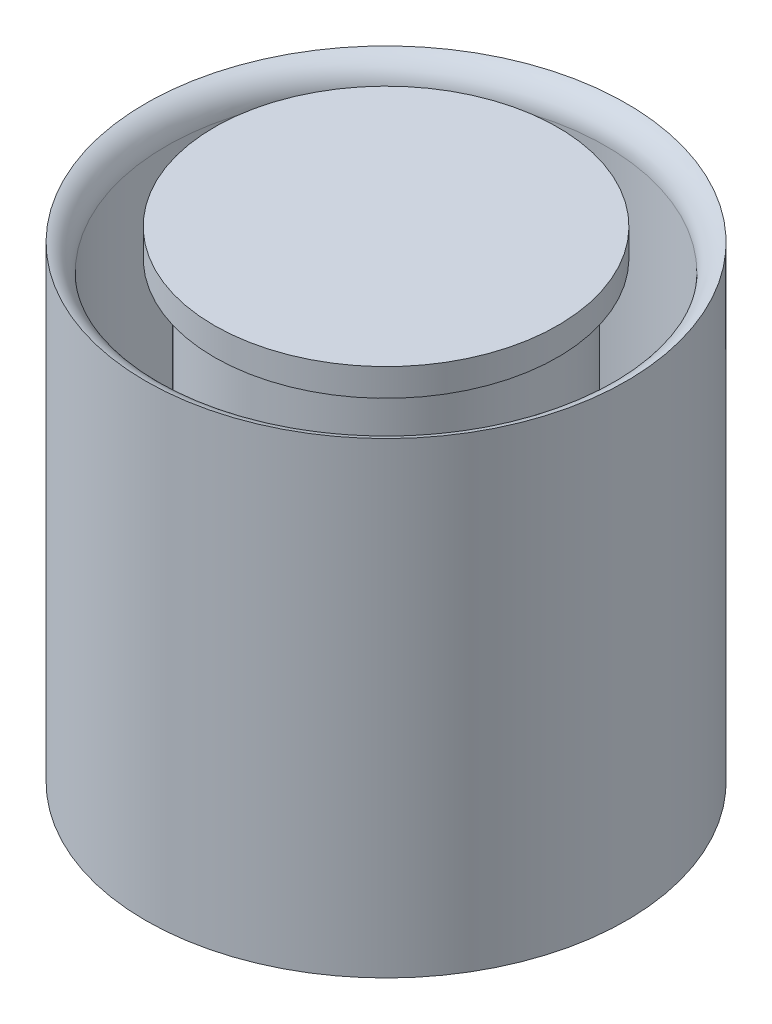
SolidWorks part; units mm, degrees
other "Markup1"
sketch "Sketch7" plane through (-27.825, 44.8441, 27.8252) normal (-0.0236, 0.9996, 0.0157) x (0.9993, 0.0241, -0.0277)
ref_plane "Alzado" through (0, 0, 0) normal (0, 0, 1) x (1, 0, 0)
ref_plane "Planta" through (0, 0, 0) normal (0, 1, 0) x (1, 0, 0)
ref_plane "Vista lateral" through (0, 0, 0) normal (1, 0, 0) x (0, 0, -1)
sketch "Sketch1" plane through (0, 0, 0) normal (0, 1, 0) x (1, 0, 0)
  circle A0 centre (0, 0) radius 17.5
  circle A1 centre (0, 0) radius 16
  dimension "D1" = 35
  dimension "D2" = 32
extrude "Boss-Extrude1" add sketch "Sketch1" along normal blind 34
sketch "Sketch2" plane through (0, 0, 0) normal (0, 1, 0) x (1, 0, 0)
  circle A0 centre (0, 0) radius 17.5
  dimension "D1" = 35
extrude "Boss-Extrude2" add sketch "Sketch2" along normal blind 3
fillet "Fillet1" radius 2 1 edges at (0, 34, 16)
ref_plane "Plane1" through (0, 3, 0) normal (0, 1, 0) x (1, 0, 0)
sketch "Sketch3" plane through (0, 3, 0) normal (0, 1, 0) x (1, 0, 0)
  circle A0 centre (0, 0) radius 11
  dimension "D1" = 22
extrude "Boss-Extrude3" add sketch "Sketch3" along normal blind 30
sketch "Sketch5" plane through (0, 33, 0) normal (0, 1, 0) x (1, 0, 0)
  line L0 (-1.0774, 1.3853) -> (1.0774, 1.3853)
  arc A0 (-1.0774, 1.3853) -> (1.0774, 1.3853) centre (0, 0) ccw
extrude "Cut-Extrude1" cut sketch "Sketch5" against normal blind 35
sketch "Sketch6" plane through (0, 33, 0) normal (0, 1, 0) x (1, 0, 0)
  line L0 (-1.3633, 1.3853) -> (1.2825, 1.3853) construction
  line L1 (-3.9815, 2.4079) -> (4.0095, 2.4079)
  line L2 (-3.9815, 2.4079) -> (-3.9815, -3.9849)
  line L3 (-3.9815, -3.9849) -> (4.0095, -3.9849)
  line L4 (4.0095, 2.4079) -> (4.0095, -3.9849)
extrude "Boss-Extrude4" add sketch "Sketch6" against normal blind 24
sketch "Sketch8" plane through (0, 33, 0) normal (0, 1, 0) x (1, 0, 0)
  circle A0 centre (0, 0) radius 12.5
  dimension "D1" = 25
sketch "Sketch9" plane through (0, 3, 0) normal (0, 1, 0) x (1, 0, 0)
  circle A0 centre (0, 0) radius 12.5
  dimension "D1" = 25
fillet "Fillet3" radius 1.5 1 edges at (0, 3, 11)
extrude "Boss-Extrude5" add sketch "Sketch8" along normal blind 2 contours A0
